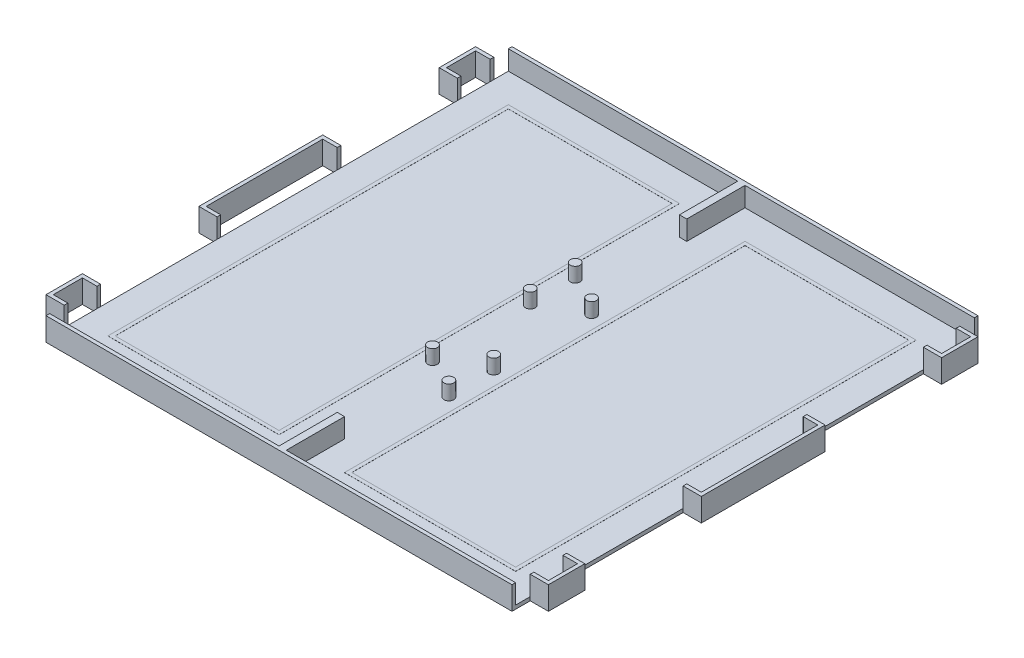
SolidWorks part; units mm, degrees
ref_plane "Front Plane" through (0, 0, 0) normal (0, 0, 1) x (1, 0, 0)
ref_plane "Top Plane" through (0, 0, 0) normal (0, 1, 0) x (1, 0, 0)
ref_plane "Right Plane" through (0, 0, 0) normal (1, 0, 0) x (0, 0, -1)
sketch "Sketch1" plane through (0, 0, 0) normal (0, 1, 0) x (1, 0, 0)
  line L1 (-120.0457, 2356.6918) -> (2318.3543, 2356.6918)
  line L2 (-120.0457, 2356.6918) -> (-120.0457, -81.7082)
  line L3 (-120.0457, -81.7082) -> (2318.3543, -81.7082)
  line L4 (2318.3543, 2356.6918) -> (2318.3543, -81.7082)
  dimension "D1" = 2438.4
  dimension "D2" = 2438.4
extrude "Boss-Extrude1" add sketch "Sketch1" along normal blind 19.05
sketch "Sketch2" plane through (0, 19.05, 0) normal (0, 1, 0) x (1, 0, 0)
  line L0 (-120.0457, -62.6582) -> (1080.1043, -62.6582)
  line L1 (-120.0457, 2356.6918) -> (-120.0457, -81.7082) construction
  line L2 (1080.1043, -62.6582) -> (1080.1043, 242.1418)
  line L3 (1080.1043, 242.1418) -> (1118.2043, 242.1418)
  line L4 (1118.2043, 242.1418) -> (1118.2043, -62.6582)
  line L5 (1118.2043, -62.6582) -> (2318.3543, -62.6582)
  line L6 (2318.3543, -81.7082) -> (2318.3543, 2356.6918) construction
  line L7 (2318.3543, -62.6582) -> (2318.3543, -81.7082)
  line L8 (2318.3543, -81.7082) -> (-120.0457, -81.7082)
  line L9 (-120.0457, -81.7082) -> (-120.0457, -62.6582)
  line L10 (-120.0457, 1137.4918) -> (2318.3543, 1137.4918) construction
  line L11 (-120.0457, 2356.6918) -> (-120.0457, 2337.6418)
  line L12 (2318.3543, 2356.6918) -> (-120.0457, 2356.6918)
  line L13 (2318.3543, 2337.6418) -> (2318.3543, 2356.6918)
  line L14 (1118.2043, 2337.6418) -> (2318.3543, 2337.6418)
  line L15 (1118.2043, 2032.8418) -> (1118.2043, 2337.6418)
  line L16 (1080.1043, 2032.8418) -> (1118.2043, 2032.8418)
  line L17 (1080.1043, 2337.6418) -> (1080.1043, 2032.8418)
  line L18 (-120.0457, 2337.6418) -> (1080.1043, 2337.6418)
  dimension "D1" = 19.05
  dimension "D2" = 38.1
  dimension "D3" = 1200.15
  dimension "D4" = 304.8
  dimension "D5" = 304.8
extrude "Boss-Extrude2" add sketch "Sketch2" along normal blind 101.6
sketch "Sketch3" plane through (0, 19.05, 0) normal (0, 1, 0) x (1, 0, 0)
  line L0 (-120.0457, 32.5918) -> (-196.2457, 32.5918)
  line L1 (-196.2457, 32.5918) -> (-196.2457, 184.9918)
  line L2 (-196.2457, 184.9918) -> (-120.0457, 184.9918)
  line L3 (-120.0457, 184.9918) -> (-120.0457, 204.0418)
  line L4 (-120.0457, 204.0418) -> (-215.2957, 204.0418)
  line L5 (-215.2957, 204.0418) -> (-215.2957, 13.5418)
  line L6 (-215.2957, 13.5418) -> (-120.0457, 13.5418)
  line L7 (-120.0457, 13.5418) -> (-120.0457, 32.5918)
  line L8 (-120.0457, 2337.6418) -> (-120.0457, -62.6582) construction
  line L9 (1080.1043, -62.6582) -> (-120.0457, -62.6582) construction
  line L10 (-120.0457, 1137.4918) -> (2318.3543, 1137.4918) construction
  line L11 (2318.3543, -62.6582) -> (2318.3543, 2337.6418) construction
  line L12 (1099.1543, 1137.4918) -> (1099.1543, -244.3363) construction
  line L13 (-120.0457, 2261.4418) -> (-120.0457, 2242.3918)
  line L14 (-215.2957, 2261.4418) -> (-120.0457, 2261.4418)
  line L15 (-215.2957, 2070.9418) -> (-215.2957, 2261.4418)
  line L16 (-120.0457, 2070.9418) -> (-215.2957, 2070.9418)
  line L17 (-120.0457, 2089.9918) -> (-120.0457, 2070.9418)
  line L18 (-196.2457, 2089.9918) -> (-120.0457, 2089.9918)
  line L19 (-196.2457, 2242.3918) -> (-196.2457, 2089.9918)
  line L20 (-120.0457, 2242.3918) -> (-196.2457, 2242.3918)
  line L21 (2318.3543, 2242.3918) -> (2394.5543, 2242.3918)
  line L22 (2394.5543, 2242.3918) -> (2394.5543, 2089.9918)
  line L23 (2394.5543, 2089.9918) -> (2318.3543, 2089.9918)
  line L24 (2318.3543, 2089.9918) -> (2318.3543, 2070.9418)
  line L25 (2318.3543, 2070.9418) -> (2413.6043, 2070.9418)
  line L26 (2413.6043, 2070.9418) -> (2413.6043, 2261.4418)
  line L27 (2413.6043, 2261.4418) -> (2318.3543, 2261.4418)
  line L28 (2318.3543, 2261.4418) -> (2318.3543, 2242.3918)
  line L29 (2318.3543, 13.5418) -> (2318.3543, 32.5918)
  line L30 (2413.6043, 13.5418) -> (2318.3543, 13.5418)
  line L31 (2413.6043, 204.0418) -> (2413.6043, 13.5418)
  line L32 (2318.3543, 204.0418) -> (2413.6043, 204.0418)
  line L33 (2318.3543, 184.9918) -> (2318.3543, 204.0418)
  line L34 (2394.5543, 184.9918) -> (2318.3543, 184.9918)
  line L35 (2394.5543, 32.5918) -> (2394.5543, 184.9918)
  line L36 (2318.3543, 32.5918) -> (2394.5543, 32.5918)
  dimension "D1" = 0
  dimension "D2" = 76.2
  dimension "D3" = 152.4
  dimension "D4" = 19.05
  dimension "D5" = 19.05
  dimension "D6" = 19.05
  dimension "D7" = 0
  dimension "D8" = 76.2
extrude "Boss-Extrude3" add sketch "Sketch3" along normal blind 101.6 and the other way blind 19.05 separate body
sketch "Sketch5" plane through (0, 19.05, 0) normal (0, 1, 0) x (1, 0, 0)
  line L0 (-120.0457, 1461.3418) -> (-215.2957, 1461.3418)
  line L1 (-120.0457, 2337.6418) -> (-120.0457, -62.6582) construction
  line L2 (-215.2957, 1461.3418) -> (-215.2957, 813.6418)
  line L3 (-215.2957, 813.6418) -> (-120.0457, 813.6418)
  line L4 (-120.0457, 813.6418) -> (-120.0457, 832.6918)
  line L5 (-120.0457, 832.6918) -> (-196.2457, 832.6918)
  line L6 (-196.2457, 832.6918) -> (-196.2457, 1442.2918)
  line L7 (-196.2457, 1442.2918) -> (-120.0457, 1442.2918)
  line L8 (-120.0457, 1442.2918) -> (-120.0457, 1461.3418)
  line L9 (2318.3543, 2356.6918) -> (-120.0457, 2356.6918) construction
  line L10 (1099.1543, 2356.6918) -> (1099.1543, -81.7082) construction
  line L11 (-120.0457, -81.7082) -> (2318.3543, -81.7082) construction
  line L12 (2318.3543, 1442.2918) -> (2318.3543, 1461.3418)
  line L13 (2394.5543, 1442.2918) -> (2318.3543, 1442.2918)
  line L14 (2394.5543, 832.6918) -> (2394.5543, 1442.2918)
  line L15 (2318.3543, 832.6918) -> (2394.5543, 832.6918)
  line L16 (2318.3543, 813.6418) -> (2318.3543, 832.6918)
  line L17 (2413.6043, 813.6418) -> (2318.3543, 813.6418)
  line L18 (2413.6043, 1461.3418) -> (2413.6043, 813.6418)
  line L19 (2318.3543, 1461.3418) -> (2413.6043, 1461.3418)
  dimension "D1" = 19.05
  dimension "D2" = 19.05
  dimension "D3" = 19.05
  dimension "D4" = 609.6
  dimension "D5" = 76.2
  dimension "D6" = 914.4
extrude "Boss-Extrude4" add sketch "Sketch5" along normal blind 101.6 and the other way blind 19.05
sketch "Sketch6" plane through (0, 19.05, 0) normal (0, 1, 0) x (1, 0, 0)
  line L0 (1099.1543, 2032.8418) -> (1099.1543, 242.1418) construction
  line L1 (1080.1043, 2032.8418) -> (1118.2043, 2032.8418) construction
  line L2 (1118.2043, 242.1418) -> (1080.1043, 242.1418) construction
  line L3 (2318.3543, 832.6918) -> (2318.3543, 813.6418) construction
  line L4 (-120.0457, 1137.4918) -> (2318.3543, 1137.4918) construction
  line L5 (-120.0457, 1442.2918) -> (-120.0457, 832.6918) construction
  line L6 (2318.3543, 832.6918) -> (2318.3543, 1442.2918) construction
  line L7 (997.5543, 823.1668) -> (1564.3701, 823.1668) construction
  line L8 (997.5543, 823.1668) -> (1200.7543, 940.4844) construction
  circle A0 centre (997.5543, 823.1668) radius 25.4
  circle A1 centre (1200.7543, 940.4844) radius 25.4
  circle A2 centre (1200.7543, 705.8492) radius 25.4
  point P8 (2318.3543, 823.1668)
  dimension "D1" = 50.8
  dimension "D4" = 50.8
  dimension "D2" = 101.6
  dimension "D3" = 0
  dimension "D5" = 101.6
  dimension "D6" = 30
extrude "Boss-Extrude5" add sketch "Sketch6" along normal blind 76.2
ref_point "Point1"
ref_axis "Axis1" through (1099.1189, 19.05, -1137.82) along (0, 1, 0)
pattern_circular "CirPattern1" count 2 over 360 about axis through (1099.1189, 19.05, -1137.82) along (0, 1, 0) of "Boss-Extrude5"
sketch "Sketch7" plane through (0, 19.05, 0) normal (0, 1, 0) x (1, 0, 0)
  line L0 (1099.1543, 2032.8418) -> (1099.1543, 242.1418) construction
  line L1 (32.3543, 2185.2418) -> (927.7043, 2185.2418)
  line L2 (32.3543, 2185.2418) -> (32.3543, 89.7418)
  line L3 (32.3543, 89.7418) -> (927.7043, 89.7418)
  line L4 (927.7043, 2185.2418) -> (927.7043, 89.7418)
  line L5 (51.4043, 2166.1918) -> (908.6543, 2166.1918)
  line L6 (51.4043, 2166.1918) -> (51.4043, 108.7918)
  line L7 (51.4043, 108.7918) -> (908.6543, 108.7918)
  line L8 (908.6543, 2166.1918) -> (908.6543, 108.7918)
  line L9 (1080.1043, 2032.8418) -> (1118.2043, 2032.8418) construction
  line L10 (1118.2043, 242.1418) -> (1080.1043, 242.1418) construction
  line L11 (-120.0457, 2337.6418) -> (1080.1043, 2337.6418) construction
  line L12 (1080.1043, -62.6582) -> (-120.0457, -62.6582) construction
  line L13 (-120.0457, 1442.2918) -> (-120.0457, 832.6918) construction
  line L14 (1080.1043, 2337.6418) -> (1080.1043, 2032.8418) construction
  line L15 (1289.6543, 2166.1918) -> (1289.6543, 108.7918)
  line L16 (2146.9043, 108.7918) -> (1289.6543, 108.7918)
  line L17 (2146.9043, 2166.1918) -> (2146.9043, 108.7918)
  line L18 (2146.9043, 2166.1918) -> (1289.6543, 2166.1918)
  line L19 (1270.6043, 2185.2418) -> (1270.6043, 89.7418)
  line L20 (2165.9543, 89.7418) -> (1270.6043, 89.7418)
  line L21 (2165.9543, 2185.2418) -> (2165.9543, 89.7418)
  line L22 (2165.9543, 2185.2418) -> (1270.6043, 2185.2418)
  dimension "D1" = 19.05
  dimension "D2" = 19.05
  dimension "D3" = 19.05
  dimension "D4" = 19.05
  dimension "D5" = 152.4
  dimension "D6" = 152.4
  dimension "D7" = 152.4
  dimension "D8" = 152.4
extrude "Boss-Extrude6" add sketch "Sketch7" along normal blind 0.5
equation "\"D2@Sketch6\"=3+(\"D1@Sketch6\"/2)"
equation "\"D5@Sketch6\"=\"D2@Sketch6\""
equation "\"D4@Sketch6\"=\"D1@Sketch6\""
